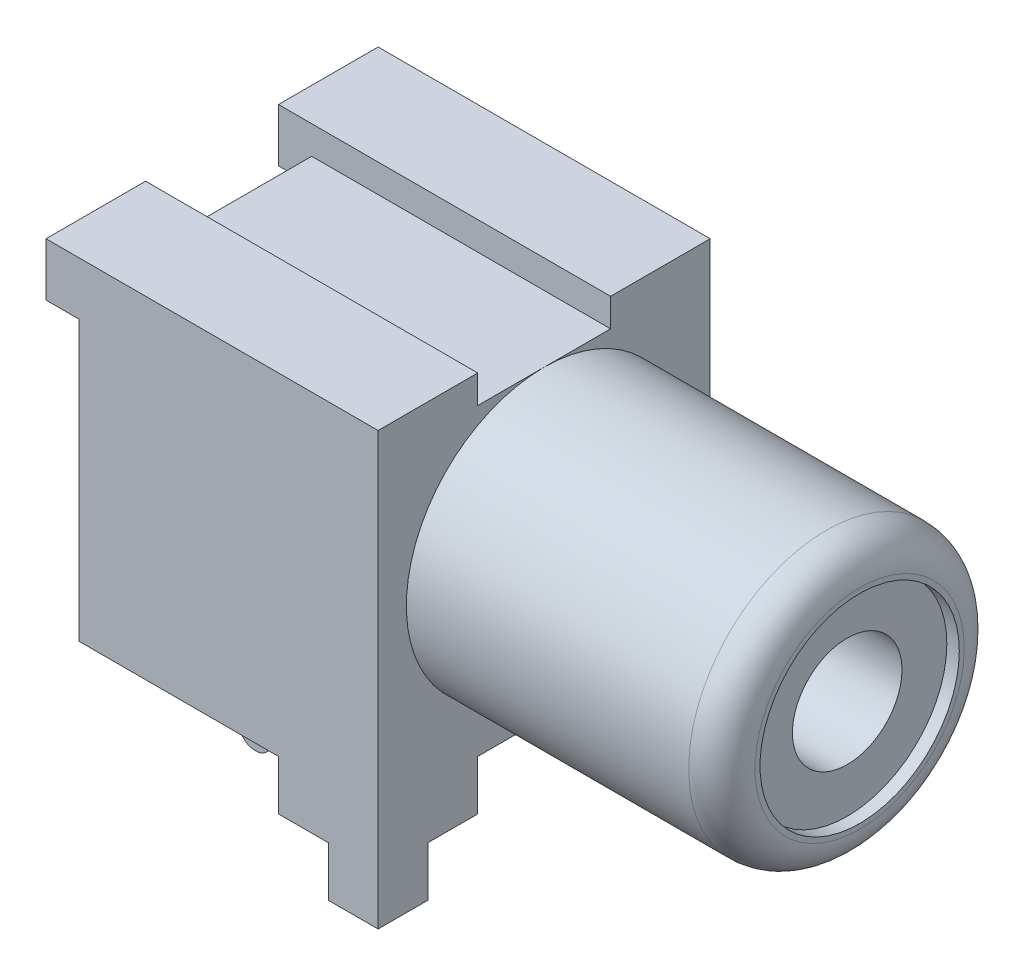
SolidWorks part; units mm, degrees
ref_plane "Plano frontal" through (0, 0, 0) normal (0, 0, 1) x (1, 0, 0)
ref_plane "Plano superior" through (0, 0, 0) normal (0, 1, 0) x (1, 0, 0)
ref_plane "Plano direito" through (0, 0, 0) normal (1, 0, 0) x (0, 0, -1)
ref_plane "Plano1" through (10, 0, 0) normal (1, 0, 0) x (0, 0, -1)
sketch "Esboço1" plane through (10, 0, 0) normal (1, 0, 0) x (0, 0, -1)
  line L0 (5, 5) -> (-5, 5)
  line L1 (-5, 5) -> (-5, -6.5)
  line L2 (-5, -6.5) -> (5, -6.5)
  line L3 (5, -6.5) -> (5, 5)
extrude "Ressalto-extrusão1" add sketch "Esboço1" against normal blind 9
sketch "Esboço2" plane through (10, 0, 0) normal (1, 0, 0) x (0, 0, -1)
  line L0 (2, 5) -> (-2, 5)
  line L1 (-2, 5) -> (-2, 4.15)
  line L2 (-2, 4.15) -> (2, 4.15)
  line L3 (2, 4.15) -> (2, 5)
extrude "Corte-extrusão1" cut sketch "Esboço2" against normal through all
sketch "Esboço3" plane through (1, 0, 0) normal (-1, 0, 0) x (0, 0, 1)
  line L0 (2, 3.4) -> (2, 5)
  line L1 (2, 5) -> (5, 5)
  line L2 (5, 5) -> (5, 3.4)
  line L3 (5, 3.4) -> (2, 3.4)
extrude "Ressalto-extrusão2" add sketch "Esboço3" along normal blind 1
sketch "Esboço4" plane through (1, 0, 0) normal (-1, 0, 0) x (0, 0, 1)
  line L0 (-5, 3.4) -> (-5, 5)
  line L1 (-5, 5) -> (-2, 5)
  line L2 (-2, 5) -> (-2, 3.4)
  line L3 (-2, 3.4) -> (-5, 3.4)
extrude "Ressalto-extrusão3" add sketch "Esboço4" along normal blind 1
sketch "Esboço5" plane through (10, 0, 0) normal (1, 0, 0) x (0, 0, -1)
  line L0 (-2, -6.5) -> (2, -6.5)
  line L1 (2, -6.5) -> (2, -5)
  line L2 (2, -5) -> (-2, -5)
  line L3 (-2, -5) -> (-2, -6.5)
extrude "Corte-extrusão2" cut sketch "Esboço5" against normal through all
sketch "Esboço6" plane through (1, 0, 0) normal (-1, 0, 0) x (0, 0, 1)
  line L0 (2, -5.5) -> (3.5, -5.5)
  line L1 (3.5, -5.5) -> (3.5, -6.5)
  line L2 (3.5, -6.5) -> (2, -6.5)
  line L3 (2, -6.5) -> (2, -5.5)
extrude "Ressalto-extrusão4" add sketch "Esboço6" along normal blind 1
sketch "Esboço7" plane through (1, 0, 0) normal (-1, 0, 0) x (0, 0, 1)
  line L0 (3.5, -5) -> (3.5, -6.5)
  line L1 (3.5, -6.5) -> (5, -6.5)
  line L2 (5, -6.5) -> (5, -5)
  line L3 (5, -5) -> (3.5, -5)
extrude "Corte-extrusão3" cut sketch "Esboço7" against normal blind 6
sketch "Esboço8" plane through (1, 0, 0) normal (-1, 0, 0) x (0, 0, 1)
  line L0 (-2, -5.5) -> (-2, -6.5)
  line L1 (-2, -6.5) -> (-3.5, -6.5)
  line L2 (-3.5, -6.5) -> (-3.5, -5.5)
  line L3 (-3.5, -5.5) -> (-2, -5.5)
extrude "Ressalto-extrusão5" add sketch "Esboço8" along normal blind 1
sketch "Esboço9" plane through (1, 0, 0) normal (-1, 0, 0) x (0, 0, 1)
  line L0 (-5, -6.5) -> (-3.5, -6.5)
  line L1 (-3.5, -6.5) -> (-3.5, -5)
  line L2 (-3.5, -5) -> (-5, -5)
  line L3 (-5, -5) -> (-5, -6.5)
extrude "Corte-extrusão4" cut sketch "Esboço9" against normal blind 6
sketch "Esboço10" plane through (0, -6.5, 0) normal (0, -1, 0) x (1, 0, 0)
  line L0 (10, 3.5) -> (8.5, 3.5)
  line L1 (8.5, 3.5) -> (8.5, 5)
  line L2 (8.5, 5) -> (10, 5)
  line L3 (10, 5) -> (10, 3.5)
extrude "Ressalto-extrusão6" add sketch "Esboço10" along normal blind 1.5
sketch "Esboço11" plane through (0, -6.5, 0) normal (0, -1, 0) x (1, 0, 0)
  line L0 (10, -5) -> (8.5, -5)
  line L1 (8.5, -5) -> (8.5, -3.5)
  line L2 (8.5, -3.5) -> (10, -3.5)
  line L3 (10, -3.5) -> (10, -5)
extrude "Ressalto-extrusão7" add sketch "Esboço11" along normal blind 1.5
sketch "Esboço12" plane through (0, 0, 0) normal (0, 0, 1) x (1, 0, 0)
  line L0 (10, 4.15) -> (10, 0)
  line L1 (10, 0) -> (19.5, 0)
  line L2 (19.5, 0) -> (19.5, 4.15)
  line L3 (19.5, 4.15) -> (10, 4.15)
  line L4 (10, 0) -> (19.5, 0) construction
revolve "Revolução1" add sketch "Esboço12" angle 360 about L4 reverse direction yes
hole_wizard "Rebaixo para parafuso de máquina de cabeça sextavada de M31" positions "Esboço14" profile "Esboço13" counterbore size "M3" standard "Ansi Metric"
sketch "Esboço14" plane through (19.5, 0, 0) normal (1, 0, 0) x (0, 0, -1)
  point P0 (0, 0)
sketch "Esboço13" plane through (19.5, 0, 0) normal (0, 1, 0) x (0, 0, -1)
  line L0 (0, 0) -> (0, 9.5)
  line L1 (0, 9.5) -> (1.65, 9.5)
  line L2 (1.65, 9.5) -> (1.65, 0.375)
  line L3 (1.65, 0.375) -> (3, 0.375)
  line L4 (3, 0.375) -> (3, 0)
  line L5 (3, 0) -> (0, 0)
  line L10 (0, 9.5) -> (-1.65, 9.5) construction
  line L11 (0, -6.35) -> (0, 107.95) construction
  dimension "Hole Dia." = 3.3
  dimension "Hole Depth" = 9.5
  dimension "C'Bore Dia." = 6
  dimension "C'Bore Depth" = 0.375
  dimension "Drill Angle" = 180
ref_plane "Plano2" through (0, 0, 0) normal (0, 0, -1) x (-1, 0, 0)
sketch "Esboço16" plane through (0, 0, 0) normal (0, 0, -1) x (-1, 0, 0)
  line L0 (-2, -5) -> (-2, -9.5)
  line L1 (-1.0193, -9.6377) -> (-0.55, -8)
  line L2 (-0.55, -8) -> (-0.8, -7.9284)
  line L3 (-0.8, -7.9284) -> (-0.8, 3.5)
  line L4 (-0.8, 3.5) -> (-1, 3.5)
  line L5 (-1, 3.5) -> (-2, -5)
  arc A0 (-2, -9.5) -> (-1.0193, -9.6377) centre (-1.5, -9.5) ccw
fillet "Filete1" radius 1 1 edges at (19.5, 0, -4.15) tangent propagation no
extrude "Ressalto-extrusão9" add sketch "Esboço16" along normal mid plane 0.4
